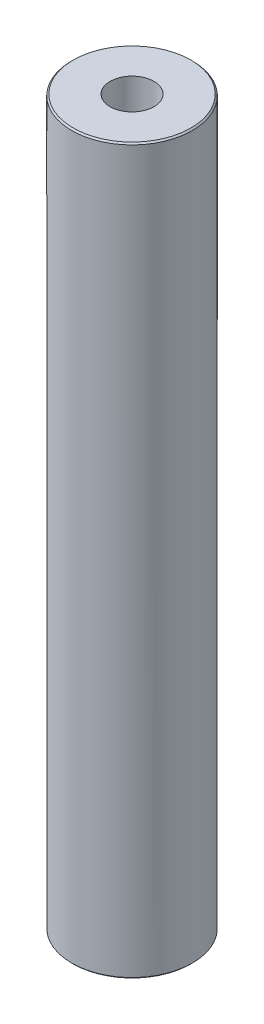
SolidWorks part; units mm, degrees
ref_plane "Front Plane" through (0, 0, 0) normal (0, 0, 1) x (1, 0, 0)
ref_plane "Top Plane" through (0, 0, 0) normal (0, 1, 0) x (1, 0, 0)
ref_plane "Right Plane" through (0, 0, 0) normal (1, 0, 0) x (0, 0, -1)
sketch "Sketch1" plane through (0, 0, 0) normal (0, 1, 0) x (1, 0, 0)
  circle A0 centre (0, 0) radius 50
  dimension "SHAFT_OD" = 100
extrude "Boss-Extrude1" add sketch "Sketch1" along normal blind 600
sketch "Sketch2" plane through (0, 0, 0) normal (0, 1, 0) x (1, 0, 0)
  circle A0 centre (0, 0) radius 18.2003
  dimension "BORE_D" = 36.4006
extrude "Cut-Extrude1" cut sketch "Sketch2" along normal through all
chamfer "Chamfer1" distance 1.1961 angle 45 2 edges at (0, 600, 50) (0, 0, 50)
